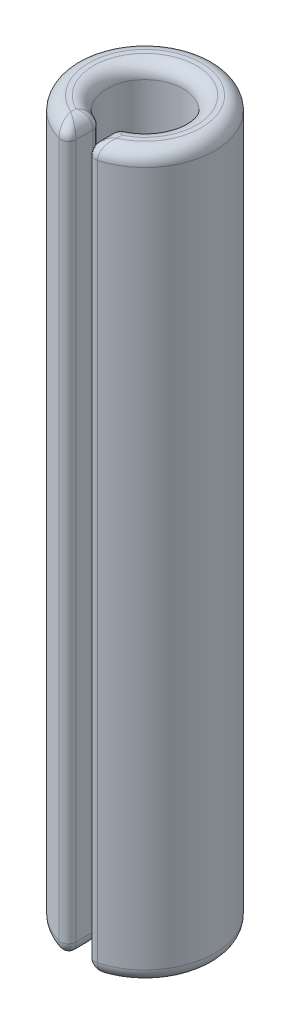
SolidWorks part; units mm, degrees
ref_plane "Front Plane" through (0, 0, 0) normal (0, 0, 1) x (1, 0, 0)
ref_plane "Top Plane" through (0, 0, 0) normal (0, 1, 0) x (1, 0, 0)
ref_plane "Right Plane" through (0, 0, 0) normal (1, 0, 0) x (0, 0, -1)
sketch "Sketch1" plane through (0, 0, 0) normal (0, 1, 0) x (1, 0, 0)
  line L0 (0, 0) -> (0, -5.3368) construction
  line L1 (-0.127, -0.5651) -> (-0.127, -0.7932)
  line L2 (0.127, -0.5651) -> (0.127, -0.7932)
  line L3 (0, 0) -> (0, -15.617) construction
  line L6 (-0.127, 0) -> (-0.127, -15.617) construction
  line L7 (0.127, 0) -> (0.127, -15.617) construction
  arc A0 (0.2567, -0.8908) -> (-0.2567, -0.8908) centre (0, 0) ccw
  arc A1 (0.1905, -0.4709) -> (-0.1905, -0.4709) centre (0, 0) ccw
  arc A2 (-0.127, -0.5651) -> (-0.1905, -0.4709) centre (-0.2286, -0.5651) ccw
  arc A3 (-0.127, -0.7932) -> (-0.2567, -0.8908) centre (-0.2286, -0.7932) cw
  arc A4 (0.2567, -0.8908) -> (0.127, -0.7932) centre (0.2286, -0.7932) cw
  arc A5 (0.1905, -0.4709) -> (0.127, -0.5651) centre (0.2286, -0.5651) ccw
  dimension "D3" = 0.1016
  dimension "D4" = 1.8542
  dimension "D5" = 1.016
  dimension "D1" = 0.127
  dimension "D2" = 0.127
extrude "Extrude1" add sketch "Sketch1" along normal blind 9.6139
fillet "Fillet1" radius 0.1778 16 edges at (0, 0, -0.508) (0.1444, 0, 0.5083) (0.127, 0, 0.6792) (0.1675, 0, 0.8744) (0, 0, -0.9271) (-0.1675, 0, 0.8744) (-0.127, 0, 0.6792) (-0.1444, 0, 0.5083) (-0.127, 9.6139, 0.6792) (-0.1675, 9.6139, 0.8744) (0, 9.6139, -0.9271) (0.1675, 9.6139, 0.8744) (0.127, 9.6139, 0.6792) (0.1444, 9.6139, 0.5083) (0, 9.6139, -0.508) (-0.1444, 9.6139, 0.5083)
